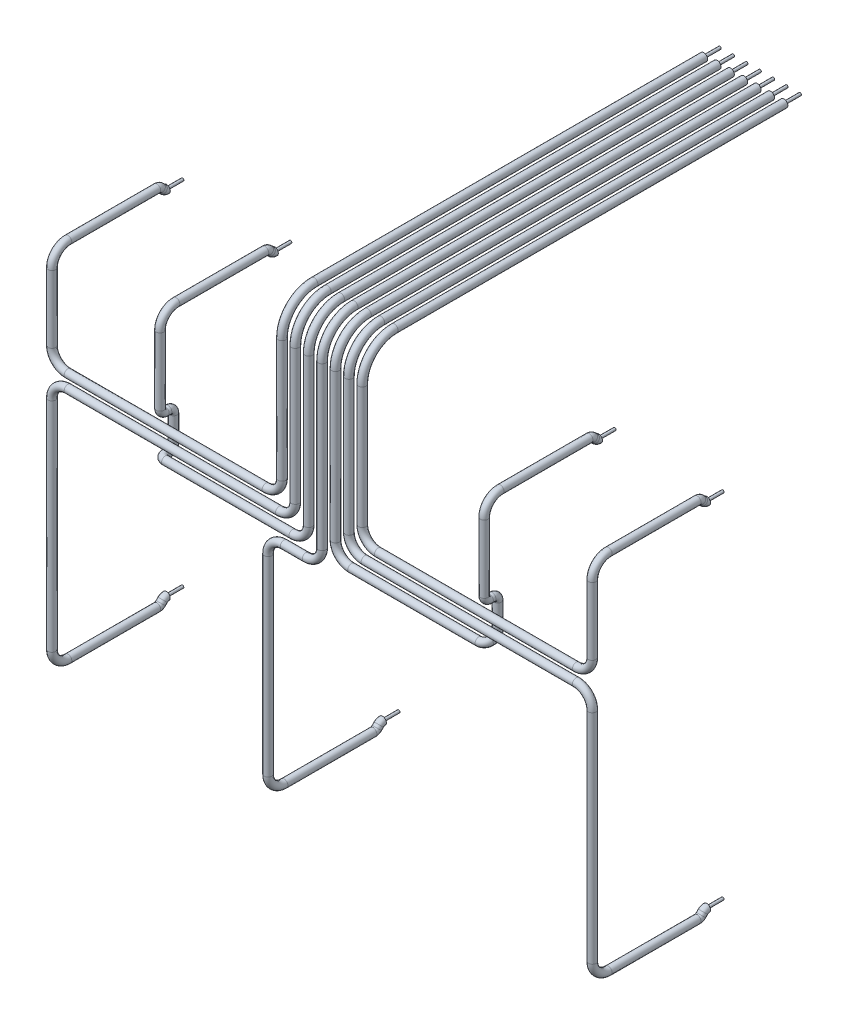
SolidWorks part; units mm, degrees
material "Copper"
ref_plane "Front" through (0, 0, 0) normal (0, 0, 1) x (1, 0, 0)
ref_plane "Top" through (0, 0, 0) normal (0, 1, 0) x (1, 0, 0)
ref_plane "Right" through (0, 0, 0) normal (1, 0, 0) x (0, 0, -1)
sketch "negative" plane through (0, 0, 0) normal (0, 0, 1) x (1, 0, 0)
  circle A0 centre (-7.5, 0) radius 0.25
  dimension "D2" = 0.5
  dimension "D1" = 7.5
sketch "Sketch2" plane through (0, 0, 0) normal (0, 0, 1) x (1, 0, 0)
  circle A0 centre (-5, 0) radius 0.25
  circle A1 centre (-7.5, 0) radius 0.25 construction
  dimension "D1" = 5
sketch "Sketch3" plane through (0, 0, 0) normal (0, 0, 1) x (1, 0, 0)
  circle A0 centre (-2.5, 0) radius 0.25
  circle A1 centre (-5, 0) radius 0.25 construction
  dimension "D1" = 2.5
sketch "middle" plane through (0, 0, 0) normal (0, 0, 1) x (1, 0, 0)
  circle A0 centre (0, 0) radius 0.25
  circle A1 centre (-2.5, 0) radius 0.25 construction
sketch3d "3DSketch1"
  line L0 (-7.5, 0, 0) -> (-7.5, 0, 75.85)
  line L1 (-7.5, -6, 81.85) -> (-7.5, -28.75, 81.85)
  line L2 (-10.5, -31.75, 81.85) -> (-47.5046, -31.75, 81.85)
  line L3 (-50.5046, -28.75, 81.85) -> (-50.5046, -16.15, 81.85)
  line L4 (-50.5046, -13.15, 78.85) -> (-50.5046, -13.15, 62.2292)
  line L5 (-50.5005, -13.4429, 61.5221) -> (-50.4953, -13.8071, 61.1577)
  line L6 (-50.4912, -14.1, 60.4506) -> (-50.4912, -14.1, 57.4506)
  arc A0 (-50.5046, -13.15, 62.2292) -> (-50.5005, -13.4429, 61.5221) centre (-50.4905, -14.1499, 62.2292) ccw
  arc A1 (-50.4953, -13.8071, 61.1577) -> (-50.4912, -14.1, 60.4506) centre (-50.5054, -13.1001, 60.4506) ccw
  arc A2 (-7.5, -28.75, 81.85) -> (-10.5, -31.75, 81.85) centre (-10.5, -28.75, 81.85) ccw
  arc A3 (-47.5046, -31.75, 81.85) -> (-50.5046, -28.75, 81.85) centre (-47.5046, -28.75, 81.85) ccw
  arc A4 (-50.5046, -16.15, 81.85) -> (-50.5046, -13.15, 78.85) centre (-50.5046, -16.15, 78.85) ccw
  arc A5 (-7.5, 0, 75.85) -> (-7.5, -6, 81.85) centre (-7.5, -6, 75.85) ccw
  point P13 (-50.5046, -13.15, 61.8149)
  point P14 (-51.4904, -14.1641, 62.2292)
  point P17 (-50.4912, -14.1, 60.8649)
  point P18 (-49.5055, -13.0859, 60.4506)
  point P24 (-7.5, -31.75, 81.85)
  point P25 (-10.5, -28.75, 78.85)
  point P28 (-50.5046, -31.75, 81.85)
  point P29 (-47.5046, -28.75, 78.85)
  point P32 (-50.5046, -13.15, 81.85)
  point P33 (-53.5046, -16.15, 78.85)
  point P36 (-7.5, 0, 81.85)
  point P37 (-1.5, -6, 75.85)
  dimension "D2" = 1
  dimension "D4" = 3
  dimension "D5" = 6
  dimension "D6" = 3
  dimension "D11" = 135
sweep "Sweep1" add profiles "negative" path "3DSketch1"
sketch "Sketch8" plane through (0, 0, 0) normal (0, 0, -1) x (-1, 0, 0)
  circle A0 centre (7.5, 0) radius 0.71
  circle A1 centre (7.5, 0) radius 0.25
  dimension "D1" = 1.42
  dimension "D2" = 0.5
sketch3d "3DSketch1<6>" same geometry as "3DSketch1"
sweep "Sweep7" add profiles "Sketch8" path "3DSketch1<7>"
sketch3d "3DSketch1<7>" same geometry as "3DSketch1"
sketch "Sketch9" plane through (0, 0, 0) normal (0, 0, -1) x (-1, 0, 0)
  circle A0 centre (7.5, 0) radius 0.71
  circle A1 centre (7.5, 0) radius 0.25
  dimension "D1" = 0.5
  dimension "D2" = 1.42
extrude "Cut-Extrude1" cut sketch "Sketch9" against normal blind 3
sketch "Sketch10" plane through (0, 0, 57.4506) normal (0, 0, -1) x (-1, 0, 0)
  circle A0 centre (50.4912, -14.1) radius 0.71
  circle A1 centre (50.4912, -14.1) radius 0.25
  dimension "D1" = 1.42
  dimension "D2" = 0.5
extrude "Cut-Extrude3" cut sketch "Sketch10" against normal blind 3
sketch3d "3DSketch2"
  line L0 (-5, 0, 0) -> (-5, 0, 75.85)
  line L1 (-5, -6, 81.85) -> (-5, -31.25, 81.85)
  line L2 (-8, -34.25, 81.85) -> (-47.499, -34.25, 81.85)
  line L3 (-50.499, -37.25, 81.85) -> (-50.499, -77.95, 81.85)
  line L4 (-50.499, -80.95, 78.85) -> (-50.499, -80.95, 62.2284)
  line L5 (-50.499, -80.6571, 61.5213) -> (-50.499, -80.2929, 61.1571)
  line L7 (-50.499, -80, 60.45) -> (-50.499, -80, 57.45)
  arc A0 (-5, 0, 75.85) -> (-5, -6, 81.85) centre (-5, -6, 75.85) ccw
  arc A1 (-50.499, -77.95, 81.85) -> (-50.499, -80.95, 78.85) centre (-50.499, -77.95, 78.85) ccw
  arc A2 (-47.499, -34.25, 81.85) -> (-50.499, -37.25, 81.85) centre (-47.499, -37.25, 81.85) ccw
  arc A3 (-5, -31.25, 81.85) -> (-8, -34.25, 81.85) centre (-8, -31.25, 81.85) ccw
  arc A4 (-50.499, -80.95, 62.2284) -> (-50.499, -80.6571, 61.5213) centre (-50.499, -79.95, 62.2284) ccw
  arc A5 (-50.499, -80.2929, 61.1571) -> (-50.499, -80, 60.45) centre (-50.499, -81, 60.45) ccw
  point P11 (-5, 0, 81.85)
  point P12 (1, -6, 75.85)
  point P15 (-50.499, -80.95, 81.85)
  point P16 (-47.499, -77.95, 78.85)
  point P19 (-50.499, -34.25, 81.85)
  point P20 (-47.499, -37.25, 84.85)
  point P23 (-5, -34.25, 81.85)
  point P24 (-8, -31.25, 78.85)
  point P32 (-50.499, -80.95, 61.8142)
  point P33 (-49.499, -79.95, 62.2284)
  point P36 (-50.499, -80, 60.8642)
  point P37 (-51.499, -81, 60.45)
  dimension "D2" = 6
  dimension "D4" = 3
  dimension "D11" = 1
  dimension "D6" = 3
  dimension "D10" = 135
sweep "Sweep8" add profiles "Sketch2" path "3DSketch2"
sketch "Sketch11" plane through (0, 0, 0) normal (0, 0, -1) x (-1, 0, 0)
  circle A0 centre (5, 0) radius 0.25
  circle A1 centre (5, 0) radius 0.71
  dimension "D1" = 0.5
  dimension "D2" = 1.42
sweep "Sweep9" add profiles "Sketch11" path "3DSketch2<2>"
sketch3d "3DSketch2<2>" same geometry as "3DSketch2"
sketch "Sketch12" plane through (0, 0, 0) normal (0, 0, -1) x (-1, 0, 0)
  circle A0 centre (5, 0) radius 0.25
  circle A1 centre (5, 0) radius 0.71
  dimension "D1" = 0.5
  dimension "D2" = 1.42
extrude "Cut-Extrude4" cut sketch "Sketch12" against normal blind 3
sketch "Sketch13" plane through (0, 0, 57.45) normal (0, 0, -1) x (-1, 0, 0)
  circle A0 centre (50.499, -80) radius 0.25
  circle A1 centre (50.499, -80) radius 0.71
  dimension "D1" = 0.5
  dimension "D2" = 1.42
extrude "Cut-Extrude7" cut sketch "Sketch13" against normal blind 3
sketch3d "3DSketch3"
  line L0 (-2.5, 0, 0) -> (-2.5, 0, 75.85)
  line L1 (-2.5, -6, 81.85) -> (-2.5, -33.75, 81.85)
  line L2 (-5.5, -36.75, 81.85) -> (-29.299, -36.75, 81.85)
  line L3 (-30.299, -36.75, 80.85) -> (-30.299, -36.75, 80.35)
  line L4 (-30.299, -35.75, 79.35) -> (-30.299, -30.8218, 79.35)
  line L5 (-30.299, -29.8218, 80.35) -> (-30.299, -29.8218, 80.85)
  line L6 (-30.299, -28.8218, 81.85) -> (-30.299, -16.15, 81.85)
  line L7 (-30.299, -13.15, 78.85) -> (-30.299, -13.15, 62.2284)
  line L8 (-30.299, -13.4429, 61.5213) -> (-30.299, -13.8071, 61.1571)
  line L9 (-30.299, -14.1, 60.45) -> (-30.299, -14.1, 57.45)
  arc A0 (-30.299, -13.15, 62.2284) -> (-30.299, -13.4429, 61.5213) centre (-30.299, -14.15, 62.2284) ccw
  arc A1 (-30.299, -13.8071, 61.1571) -> (-30.299, -14.1, 60.45) centre (-30.299, -13.1, 60.45) ccw
  arc A2 (-30.299, -16.15, 81.85) -> (-30.299, -13.15, 78.85) centre (-30.299, -16.15, 78.85) ccw
  arc A3 (-2.5, -33.75, 81.85) -> (-5.5, -36.75, 81.85) centre (-5.5, -33.75, 81.85) ccw
  arc A4 (-30.299, -30.8218, 79.35) -> (-30.299, -29.8218, 80.35) centre (-30.299, -30.8218, 80.35) ccw
  arc A5 (-30.299, -29.8218, 80.85) -> (-30.299, -28.8218, 81.85) centre (-30.299, -28.8218, 80.85) ccw
  arc A6 (-30.299, -36.75, 80.35) -> (-30.299, -35.75, 79.35) centre (-30.299, -35.75, 80.35) ccw
  arc A7 (-29.299, -36.75, 81.85) -> (-30.299, -36.75, 80.85) centre (-29.299, -36.75, 80.85) ccw
  arc A8 (-2.5, 0, 75.85) -> (-2.5, -6, 81.85) centre (-2.5, -6, 75.85) ccw
  point P17 (-30.299, -13.15, 61.8142)
  point P18 (-31.299, -14.15, 62.2284)
  point P21 (-30.299, -14.1, 60.8642)
  point P22 (-29.299, -13.1, 60.45)
  point P25 (-30.299, -13.15, 81.85)
  point P26 (-33.299, -16.15, 78.85)
  point P29 (-2.5, -36.75, 81.85)
  point P30 (-5.5, -33.75, 78.85)
  point P34 (-30.299, -29.8218, 79.35)
  point P35 (-29.299, -30.8218, 80.35)
  point P38 (-30.299, -29.8218, 81.85)
  point P39 (-31.299, -28.8218, 80.85)
  point P42 (-30.299, -36.75, 79.35)
  point P43 (-29.299, -35.75, 80.35)
  point P46 (-30.299, -36.75, 81.85)
  point P47 (-29.299, -37.75, 80.85)
  point P50 (-2.5, 0, 81.85)
  point P51 (3.5, -6, 75.85)
  dimension "D10" = 1
  dimension "D12" = 3
  dimension "D14" = 1
  dimension "D16" = 6
  dimension "D8" = 135
  dimension "D11" = 3
  dimension "D13" = 2.5
  dimension "D15" = 7
sweep "Sweep10" add profiles "Sketch3" path "3DSketch3"
sketch "Sketch14" plane through (0, 0, 0) normal (0, 0, -1) x (-1, 0, 0)
  circle A0 centre (2.5, 0) radius 0.25
  circle A1 centre (2.5, 0) radius 0.71
  dimension "D1" = 0.5
  dimension "D2" = 1.42
sweep "Sweep11" add profiles "Sketch14" path "3DSketch3<2>"
sketch3d "3DSketch3<2>" same geometry as "3DSketch3"
sketch "Sketch15" plane through (0, 0, 57.45) normal (0, 0, -1) x (-1, 0, 0)
  circle A0 centre (30.299, -14.1) radius 0.25
  circle A1 centre (30.299, -14.1) radius 0.71
  dimension "D1" = 0.5
  dimension "D2" = 1.42
extrude "Cut-Extrude8" cut sketch "Sketch15" against normal blind 3
sketch "Sketch16" plane through (0, 0, 0) normal (0, 0, -1) x (-1, 0, 0)
  circle A0 centre (2.5, 0) radius 0.25
  circle A1 centre (2.5, 0) radius 0.71
  dimension "D1" = 0.5
  dimension "D2" = 1.42
extrude "Cut-Extrude9" cut sketch "Sketch16" against normal blind 3
sketch3d "3DSketch4"
  line L0 (0, 0, 0) -> (0, 0, 75.85)
  line L1 (0, -6, 81.85) -> (0, -36.25, 81.85)
  line L2 (-3, -39.25, 81.85) -> (-7.099, -39.25, 81.85)
  line L3 (-10.099, -42.25, 81.85) -> (-10.099, -77.95, 81.85)
  line L4 (-10.099, -80.95, 78.85) -> (-10.099, -80.95, 62.2284)
  line L5 (-10.099, -80.6571, 61.5213) -> (-10.099, -80.2929, 61.1571)
  line L6 (-10.099, -80, 60.45) -> (-10.099, -80, 57.45)
  arc A0 (-10.099, -80.95, 62.2284) -> (-10.099, -80.6571, 61.5213) centre (-10.099, -79.95, 62.2284) ccw
  arc A1 (-10.099, -80.2929, 61.1571) -> (-10.099, -80, 60.45) centre (-10.099, -81, 60.45) ccw
  arc A2 (-10.099, -77.95, 81.85) -> (-10.099, -80.95, 78.85) centre (-10.099, -77.95, 78.85) ccw
  arc A3 (-7.099, -39.25, 81.85) -> (-10.099, -42.25, 81.85) centre (-7.099, -42.25, 81.85) ccw
  arc A4 (0, -36.25, 81.85) -> (-3, -39.25, 81.85) centre (-3, -36.25, 81.85) ccw
  arc A5 (0, 0, 75.85) -> (0, -6, 81.85) centre (0, -6, 75.85) ccw
  point P11 (-10.099, -80.95, 61.8142)
  point P12 (-9.099, -79.95, 62.2284)
  point P15 (-10.099, -80, 60.8642)
  point P16 (-11.099, -81, 60.45)
  point P19 (-10.099, -80.95, 81.85)
  point P20 (-7.099, -77.95, 78.85)
  point P23 (-10.099, -39.25, 81.85)
  point P24 (-7.099, -42.25, 84.85)
  point P27 (0, -39.25, 81.85)
  point P28 (-3, -36.25, 78.85)
  point P31 (0, 0, 81.85)
  point P32 (6, -6, 75.85)
  dimension "D5" = 1
  dimension "D11" = 3
  dimension "D12" = 6
  dimension "D4" = 135
  dimension "D6" = 3
sweep "Sweep12" add profiles "middle" path "3DSketch4"
sketch "Sketch17" plane through (0, 0, 0) normal (0, 0, -1) x (-1, 0, 0)
  circle A0 centre (0, 0) radius 0.25
  circle A1 centre (0, 0) radius 0.71
  dimension "D1" = 0.5
  dimension "D2" = 1.42
sweep "Sweep13" add profiles "Sketch17" path "3DSketch4<3>"
sketch3d "3DSketch4<3>" same geometry as "3DSketch4"
sketch "Sketch18" plane through (0, 0, 0) normal (0, 0, -1) x (-1, 0, 0)
  circle A0 centre (0, 0) radius 0.25
  circle A1 centre (0, 0) radius 0.71
  dimension "D1" = 0.5
  dimension "D2" = 1.42
extrude "Cut-Extrude10" cut sketch "Sketch18" against normal blind 3
sketch "Sketch19" plane through (0, 0, 57.45) normal (0, 0, -1) x (-1, 0, 0)
  circle A0 centre (10.099, -80) radius 0.25
  circle A1 centre (10.099, -80) radius 0.71
  dimension "D1" = 0.5
  dimension "D2" = 1.42
extrude "Cut-Extrude11" cut sketch "Sketch19" against normal blind 3
mirror "Mirror2" about plane through (0, 0, 0) normal (1, 0, 0) of bodies 116 119 108 115 107 101
